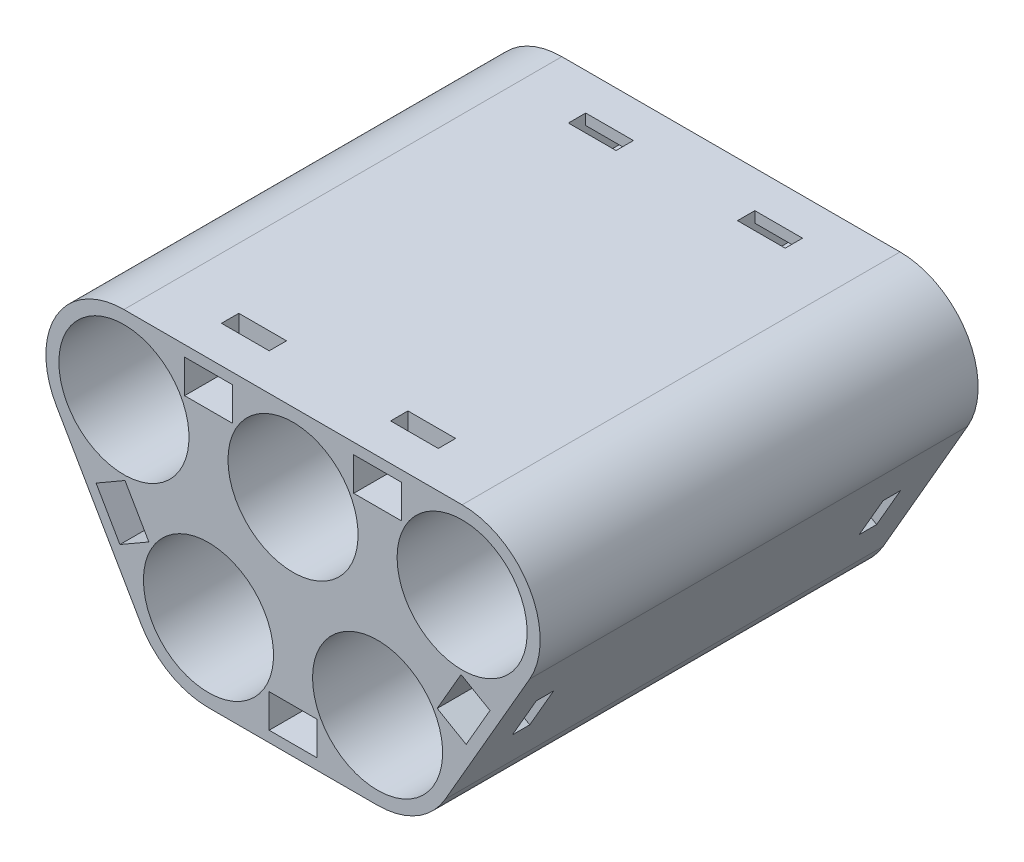
SolidWorks part; units mm, degrees
ref_plane "Front Plane" through (0, 0, 0) normal (0, 0, 1) x (1, 0, 0)
ref_plane "Top Plane" through (0, 0, 0) normal (0, 1, 0) x (1, 0, 0)
ref_plane "Right Plane" through (0, 0, 0) normal (1, 0, 0) x (0, 0, -1)
sketch "Sketch1" plane through (0, 0, 0) normal (0, 0, 1) x (1, 0, 0)
  line L0 (0, 9) -> (39, 9) construction
  line L1 (1.9558, -21.3875) -> (-7.7942, -4.5) construction
  line L2 (29.25, -25.8875) -> (9.75, -25.8875) construction
  line L3 (46.7942, -4.5) -> (37.0442, -21.3875) construction
  line L4 (0, 9) -> (39, 9)
  line L5 (1.9558, -21.3875) -> (-7.7942, -4.5)
  line L6 (29.25, -25.8875) -> (9.75, -25.8875)
  line L7 (46.7942, -4.5) -> (37.0442, -21.3875)
  arc A0 (46.7942, -4.5) -> (39, 9) centre (39, 0) ccw construction
  arc A1 (0, 9) -> (-7.7942, -4.5) centre (0, 0) ccw construction
  arc A2 (1.9558, -21.3875) -> (9.75, -25.8875) centre (9.75, -16.8875) ccw construction
  arc A3 (29.25, -25.8875) -> (37.0442, -21.3875) centre (29.25, -16.8875) ccw construction
  arc A4 (46.7942, -4.5) -> (39, 9) centre (39, 0) ccw
  arc A5 (0, 9) -> (-7.7942, -4.5) centre (0, 0) ccw
  arc A6 (1.9558, -21.3875) -> (9.75, -25.8875) centre (9.75, -16.8875) ccw
  arc A7 (29.25, -25.8875) -> (37.0442, -21.3875) centre (29.25, -16.8875) ccw
  circle A8 centre (0, 0) radius 7.5 construction
  circle A9 centre (9.75, -16.8875) radius 7.5 construction
  circle A10 centre (19.5, 0) radius 7.5 construction
  circle A11 centre (39, 0) radius 7.5 construction
  circle A12 centre (29.25, -16.8875) radius 7.5 construction
  circle A13 centre (0, 0) radius 7.5
  circle A14 centre (9.75, -16.8875) radius 7.5
  circle A15 centre (19.5, 0) radius 7.5
  circle A16 centre (39, 0) radius 7.5
  circle A17 centre (29.25, -16.8875) radius 7.5
extrude "Boss-Extrude1" add sketch "Sketch1" along normal up to surface (50.5 mm away)
sketch "Sketch2" plane through (37.0442, -21.3875, 0) normal (0.866, -0.5, 0) x (0, 0, -1)
  line L0 (0, 0) -> (0, 19.5) construction
  line L1 (0, 0) -> (0, 19.5)
  line L2 (-4.25, 7) -> (-6.25, 7)
  line L3 (-4.5, 12.25) -> (-6, 12.25)
  line L4 (-4.5, 12.25) -> (-4.5, 7.25)
  line L5 (-4.5, 7.25) -> (-6, 7.25)
  line L6 (-6, 12.25) -> (-6, 7.25)
  line L7 (-6.25, 12.5) -> (-6.25, 7)
  line L8 (-4.25, 12.5) -> (-6.25, 12.5)
  line L9 (-4.25, 12.5) -> (-4.25, 7)
  dimension "D1" = 1.5
  dimension "D2" = 0.25
extrude "Cut-Extrude1" cut sketch "Sketch2" against normal blind 1.5 contours L9 L2 L7 L8
sketch "Sketch3" plane through (0, 9, 0) normal (0, 1, 0) x (1, 0, 0)
  line L0 (32, -4.25) -> (32, -6.25)
  line L1 (31.75, -4.5) -> (26.75, -4.5)
  line L2 (31.75, -4.5) -> (31.75, -6)
  line L3 (31.75, -6) -> (26.75, -6)
  line L4 (26.75, -4.5) -> (26.75, -6)
  line L5 (32, -6.25) -> (26.5, -6.25)
  line L6 (26.5, -4.25) -> (26.5, -6.25)
  line L7 (32, -4.25) -> (26.5, -4.25)
  dimension "D1" = 1.5
  dimension "D2" = 0.25
extrude "Cut-Extrude2" cut sketch "Sketch3" against normal blind 1.5 contours L7 L6 L5 L0
sketch "Sketch4" plane through (0, -25.8875, 0) normal (0, -1, 0) x (1, 0, 0)
  line L8 (22.25, 4.25) -> (22.25, 6.25)
  line L9 (22.25, 6.25) -> (16.75, 6.25)
  line L10 (16.75, 6.25) -> (16.75, 4.25)
  line L11 (16.75, 4.25) -> (22.25, 4.25)
  line L12 (22.25, 4.25) -> (22.25, 6.25)
  line L13 (22.25, 6.25) -> (16.75, 6.25)
  line L14 (16.75, 6.25) -> (16.75, 4.25)
  line L15 (16.75, 4.25) -> (22.25, 4.25)
  dimension "D1" = 0.25
extrude "Cut-Extrude3" cut sketch "Sketch4" against normal blind 1.5
sketch "Sketch5" plane through (0, 0, 0) normal (0, 0, -1) x (-1, 0, 0)
  line L0 (-41.8702, -10.0287) -> (-39.3702, -14.3588)
  line L1 (-41.8702, -10.0287) -> (-38.9655, -8.3516)
  line L2 (-39.3702, -14.3588) -> (-36.4655, -12.6818)
  line L3 (-38.9655, -8.3516) -> (-36.4655, -12.6818)
  line L4 (-42.2117, -9.9372) -> (-39.4617, -14.7003)
  line L5 (-39.4617, -14.7003) -> (-36.1239, -12.7733)
  line L6 (-38.8739, -8.0101) -> (-36.1239, -12.7733)
  line L7 (-42.2117, -9.9372) -> (-38.8739, -8.0101)
  line L8 (-31.75, 7.5) -> (-26.75, 7.5) construction
  line L9 (-22, -24.3875) -> (-17, -24.3875) construction
  line L10 (-32, 7.75) -> (-26.5, 7.75)
  line L11 (-32, 7.75) -> (-32, 3.8959)
  line L12 (-32, 3.8959) -> (-26.5, 3.8959)
  line L13 (-26.5, 7.75) -> (-26.5, 3.8959)
  line L14 (-32, 7.75) -> (-26.5, 3.8959) construction
  line L15 (-32, 3.8959) -> (-26.5, 7.75) construction
  line L17 (-22.25, -20.7834) -> (-16.75, -20.7834)
  line L18 (-22.25, -20.7834) -> (-22.25, -24.6375)
  line L19 (-22.25, -24.6375) -> (-16.75, -24.6375)
  line L20 (-16.75, -20.7834) -> (-16.75, -24.6375)
  line L21 (-22.25, -20.7834) -> (-16.75, -24.6375) construction
  line L22 (-22.25, -24.6375) -> (-16.75, -20.7834) construction
  point P14 (-29.25, 5.8229)
  point P20 (-29.25, 7.5)
  point P24 (-19.5, -22.7104)
  point P30 (-19.5, -24.3875)
  dimension "D1" = 3.3541
  dimension "D3" = 0.25
  dimension "D4" = 0.25
  dimension "D2" = 0.25
extrude "Cut-Extrude4" cut sketch "Sketch5" against normal blind 6.25 contours L13 L10 L11 L12 | L20 L17 L18 L19 | L6 L5 L4 L7 region at (29.25, 5.8229, 0) region at (19.5, -22.7104, 0)
ref_plane "Plane1" through (19.5, 0, 0) normal (-1, 0, 0) x (0, 0, 1)
mirror "Mirror2" about plane through (19.5, 0, 0) normal (-1, 0, 0) of "Cut-Extrude4", "Cut-Extrude3", "Cut-Extrude2", "Cut-Extrude1"
ref_plane "Plane2" through (0, 0, 25.25) normal (0, 0, -1) x (-1, 0, 0)
mirror "Mirror3" about plane through (0, 0, 25.25) normal (0, 0, -1) of "Mirror2", "Cut-Extrude4", "Cut-Extrude3", "Cut-Extrude2", "Cut-Extrude1"
equation "\"D1@Sketch5\"=sqr( 5)*1.5"
equation "\"D1@Cut-Extrude4\"=6.00mm+.25"
